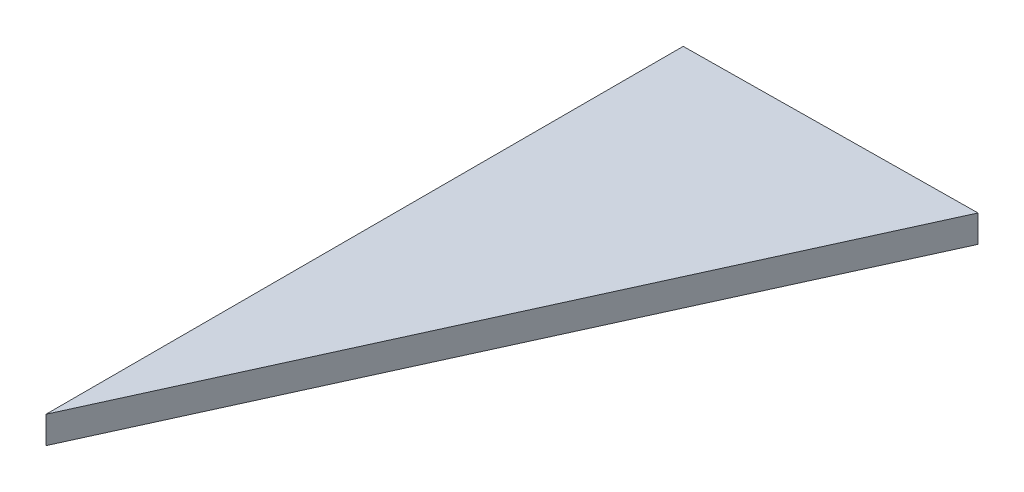
SolidWorks part; units mm, degrees
ref_plane "Front Plane" through (0, 0, 0) normal (0, 0, 1) x (1, 0, 0)
ref_plane "Top Plane" through (0, 0, 0) normal (0, 1, 0) x (1, 0, 0)
ref_plane "Right Plane" through (0, 0, 0) normal (1, 0, 0) x (0, 0, -1)
sketch "Sketch1" plane through (0, 0, 0) normal (0, 1, 0) x (1, 0, 0)
  line L1 (0, 0) -> (263.3435, 0)
  line L2 (0, 0) -> (0, 204.1914)
  line L3 (0, 204.1914) -> (263.3435, 204.1914)
  line L4 (263.3435, 0) -> (263.3435, 204.1914)
  line L5 (0, 0) -> (263.3435, 204.1914) construction
  line L6 (0, 204.1914) -> (263.3435, 0) construction
  point P4 (131.6717, 102.0957)
  dimension "D1" = 263.3435
  dimension "D2" = 204.1914
extrude "Boss-Extrude1" add sketch "Sketch1" along normal blind 4.6
sketch "Sketch2" plane through (0, 4.6, 0) normal (0, 1, 0) x (1, 0, 0)
  line L8 (-37.0799, 19.9863) -> (0, 19.9863)
  line L9 (-37.0799, 127.6823) -> (-37.0799, 19.9863)
  line L10 (0, 127.6823) -> (-37.0799, 127.6823)
  line L11 (0, 19.9863) -> (0, 127.6823)
  line L12 (75.1968, 156.7054) -> (100.9033, 128.4211)
  line L13 (75.1968, 156.7054) -> (49.2975, 128.209)
  line L14 (49.2975, 128.209) -> (75.004, 99.9247)
  line L15 (100.9033, 128.4211) -> (75.004, 99.9247)
  line L18 (0, 204.1914) -> (0, 0)
  line L19 (65.2945, -51.8558) -> (0, 19.9863)
  line L20 (0, 19.9863) -> (49.2975, 128.209)
  line L21 (0, 127.6823) -> (49.2975, 128.209)
  line M9 (0, 204.1914) -> (0, 0)
extrude "Cut-Extrude1" cut sketch "Sketch2" against normal through all flip side to cut contours L21 L20 M9 region at (16.4325, 4.6, -91.9592)
equation "\"MDF\"= 4.8mm"
equation "\"Foamcore\"= 4.6mm"
equation "\"GMaterial\"= \"MDF\""
equation "\"PCB\" = 1.6mm"
equation "\"BaseWidth\" = 10in"
equation "\"SkidLength\" = 1in"
equation "\"SkidClearance\" = 0.4in"
equation "\"MotorMountLength\" = 2in"
equation "\"MotorMountWidth\" = \"GMaterial\""
equation "\"MotorMountHeight\" = 2.25in"
equation "\"UnoStackWidth\" = 77.4mm"
equation "\"UnoStackLength\" = 79.8mm"
equation "\"UnoStackHeight\" = 34.2mm"
equation "\"TallHexRiserHeight\" = 22.2mm"
equation "\"PingPongBallSize\" = 40mm"
equation "\"BarrelLength\" = 9in"
equation "\"BarrelSize\" = \"PingPongBallSize\""
equation "\"PlatformLength\" = 4in"
equation "\"PlatformWidth\" = 6in"
equation "\"WheelDiameter\"=2.99213"
equation "\"ServoMountHeight\"=2.49223"
equation "\"ServoGearHeight\" = 0.95330261in"
equation "\"ServoMountLength\"= 1.53774"
equation "\"PivotHoleRadius\"= 0.616358"
equation "\"PlatformMountHeight\" = 3.19"
equation "\"TensionOffSet\"= .3mm"
equation "\"MotorMountWedge\"=0.333333"
equation "\"LaserCutterOffset\"= .3mm"
equation "\"BumperWidth\"=11"
equation "\"PitcherWheelCompression\" = 2.5mm"
equation "\"BarrelToHopperDistance\" = 0.5405in"
equation "\"PitchingWheelWidth\" = 26.2mm"
equation "\"PitchingWheelDiameter\" = 65.5mm"
equation "\"PitchingWheelMountOffset\" = 8.4mm"
equation "\"PitchingWheelInnerDiameter\" = 45.5mm"
equation "\"PitchingWheelBoltShoulder\" = 4.5mm"
equation "\"BrassCouplingLength\" = 18mm"
equation "\"PitchingMotorHeight\" = 57.0mm"
equation "\"PitchingMotorShaftTopHeight\" = \"PitchingMotorHeight\" - 44.1mm"
equation "\"PitchingMotorBodyHeight\" = 38mm"
equation "\"PitchingMotorTopShoulderHeight\" = 40.6mm - \"PitchingMotorBodyHeight\" "
equation "\"PitchingMotorBottomShoulderHeight\" = 40.2mm - \"PitchingMotorBodyHeight\""
equation "\"PitchingMotorBottomShaftHeight\" = \"PitchingMotorHeight\" - \"PitchingMotorShaftTopHeight\" - \"PitchingMotorTopShoulderHeight\" - \"PitchingMotorBodyHeight\" - \"PitchingMotorBottomShoulderHeight\""
equation "\"PitchingMotorShaftDiameter\" = 2.2mm"
equation "\"PitchingMotorBodyDiameter\" = 27.4mm"
equation "\"PitchingMotorTopShoulderDiameter\" = 9.8mm"
equation "\"PitchingMotorBottomShoulderDiameter\" = 9.8mm"
equation "\"BrassCouplingHexSize\" = 12mm"
equation "\"BrassCouplingBoreSize\" = 3.17mm"
equation "\"PitchingMotorMountingHoleDistance\" = 16mm"
equation "\"Acrylic\" = 4.4mm"
equation "\"PitchingMotorDistance\" = \"PitchingWheelDiameter\" + \"PingPongBallSize\" - \"PitcherWheelCompression\"*2"
equation "\"PitchingMotorPlatformOffset\"=1"
equation "\"ServoPlatformOffset\"=1.64173"
equation "\"BallBearingDiameter\" = 22mm"
equation "\"BallBearingWidth\" = 9mm"
equation "\"BallBearingHexShoulder\" = 9mm - 5.9mm"
equation "\"BallBearingHexSize\" = .36in"
equation "\"PlatformMountFootLength\"=0.857143"
equation "\"WheelWidth\"= 26mm"
equation "\"ServoMountReductionBackHeight\"=2.25"
equation "\"PlatformBottomWidthThird\" =  0.857143in"
equation "\"PlatformMountBackReductionHeight\"= 2.5in"
equation "\"PlatformMountBackReductionWidth\"= 3/7in"
equation "\"PlatformMountFrontReductionWidth\" =  1.46226in"
equation "\"PlatformMountFrontReductionHeight\" = 2.5in"
equation "\"HopperLongWallLength\" = 8.646in"
equation "\"HopperShortWallLength\" = 0.9571in"
equation "\"HopperHeight\" = 3.50in - \"Foamcore\""
equation "\"HoperLongSlantLength\" = 7.064in"
equation "\"HopperBottomTemplateWidth\" = 8.03903165in"
equation "\"HopperBottomTemplateLength\" = 10.367854in"
equation "\"D1@Sketch1\"=\"HopperBottomTemplateLength\""
equation "\"D2@Sketch1\"=\"HopperBottomTemplateWidth\""
equation "\"D1@Boss-Extrude1\"=\"Foamcore\""
